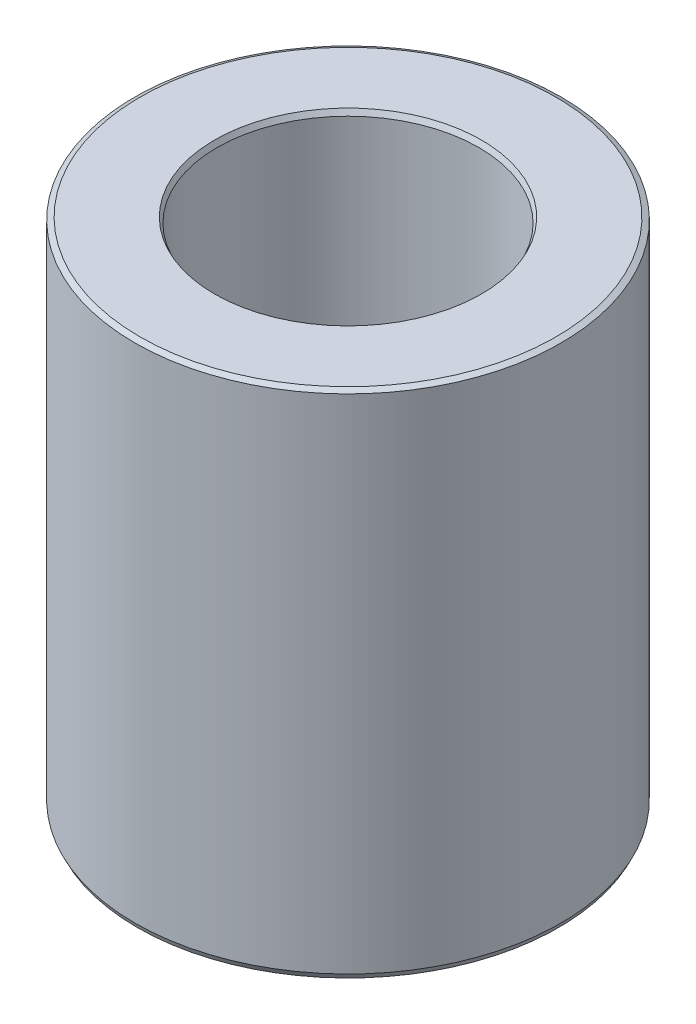
SolidWorks part; units mm, degrees
ref_plane "Front Plane" through (0, 0, 0) normal (0, 0, 1) x (1, 0, 0)
ref_plane "Top Plane" through (0, 0, 0) normal (0, 1, 0) x (1, 0, 0)
ref_plane "Right Plane" through (0, 0, 0) normal (1, 0, 0) x (0, 0, -1)
sketch "Sketch1" plane through (0, 0, 0) normal (0, 1, 0) x (1, 0, 0)
  circle A0 centre (0, 0) radius 60
  dimension "SLEEVE_OD" = 120
extrude "Boss-Extrude1" add sketch "Sketch1" along normal blind 143.6635
sketch "Sketch2" plane through (0, 0, 0) normal (0, 1, 0) x (1, 0, 0)
  circle A0 centre (0, 0) radius 36.8566
  dimension "BORE_D" = 73.7132
extrude "Cut-Extrude1" cut sketch "Sketch2" along normal through all
chamfer "Chamfer1" distance 0.7173 angle 64.124 4 edges at (0, 143.6635, 36.8566) (0, 0, 36.8566) (0, 0, 60) (0, 143.6635, 60) first distance on face at (0, 143.6635, 36.8566) first distance on face at (0, 0, 36.8566) first distance on face at (0, 143.6635, 60)
